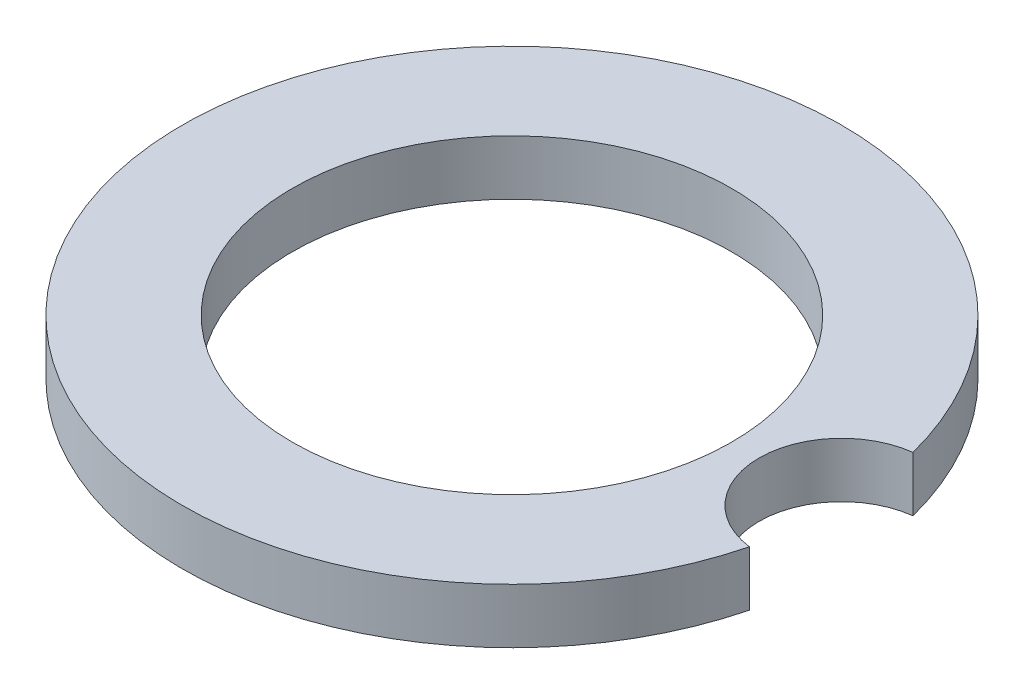
SolidWorks part; units mm, degrees
ref_plane "Front Plane" through (0, 0, 0) normal (0, 0, 1) x (1, 0, 0)
ref_plane "Top Plane" through (0, 0, 0) normal (0, 1, 0) x (1, 0, 0)
ref_plane "Right Plane" through (0, 0, 0) normal (1, 0, 0) x (0, 0, -1)
sketch "Sketch1" plane through (0, 0, 0) normal (0, 1, 0) x (1, 0, 0)
  circle A0 centre (0, 0) radius 50.8
  circle A1 centre (0, 0) radius 76.1746
  dimension "Front_CR_ID" = 101.6
  dimension "Front_CR_OD" = 152.3492
extrude "Boss-Extrude1" add sketch "Sketch1" along normal blind 12.7 contours A1
extrude "Cut-Extrude2" cut sketch "Sketch1<10>" along normal through all contours A0
sketch "Sketch1<10>" plane through (0, 0, 0) normal (0, 1, 0) x (1, 0, 0) same geometry as "Sketch1"
sketch "Sketch2" plane through (0, 12.7, 0) normal (0, 1, 0) x (1, 0, 0)
  line L0 (76.2, 19.05) -> (76.2, -19.05)
  arc A0 (76.2, 19.05) -> (76.2, -19.05) centre (76.1746, 0) ccw
  circle A1 centre (0, 0) radius 76.1746 construction
  dimension "D1" = 38.1
extrude "Cut-Extrude3" cut sketch "Sketch2" against normal through all contours A0 L0
equation "\"Bodytube_OD\" = 6.17in"
equation "\"Bodytube_ID\" = 5.998in"
equation "\"Motor_OD\" = 4in"
equation "\"Fwd_Tube_Length\" = 38in"
equation "\"Mid_Tube_Length\" = 8in"
equation "\"Aft_Section_Length\"= 40in"
equation "\"Mid_Coupler_Length\" = 13in"
equation "\"Aft_Lower_Length\"= 22in"
equation "\"AB_Coupler_OD_Length\"= 1in"
equation "\"AB_Coupling_Section_Length\"= 0.375in"
equation "\"AB_Coupler_Length\"= \"AB_Coupler_OD_Length\" + \"AB_Coupling_Section_Length\" * 2"
equation "\"Cutout_Angle\" = 80"
equation "\"AB_Paddle_Height\" = 0.375in"
equation "\"AB_Coupler_Num_Screws\"= 6"
equation "\"Num_Cutouts\" = 3"
equation "\"AB_Coupler_OD\"= 6.17in"
equation "\"AB_Coupler_ID\"= 5.75in"
equation "\"AB_Coupler_Surface_Diameter\"= 5.998in"
equation "\"AB_Coupling_Screw_Diameter\"= 0.1065in"
equation "\"AB_Central_Bushing_Length\" = .75in"
equation "\"Lead_Screw_Dist\" = 2.25in"
equation "\"Lead_Screw_Diam\" = (27/64)*1in"
equation "\"Lead_Screw_Length\" = (\"Mid_Coupler_Length\" + 2*0.375in + 2*0.5in)"
equation "\"Paddle_Pin_Offset\" = .25in"
equation "\"Paddle_Pin_Radius\" = 2.25in"
equation "\"Paddle_Gear_OD\" = 3.2in"
equation "\"Fwd_BKHD_From_Top\" = 18in"
equation "\"Front_CR_OD@Sketch1\"=\"Bodytube_ID\""
equation "\"Front_CR_ID@Sketch1\"=\"Motor_OD\""
